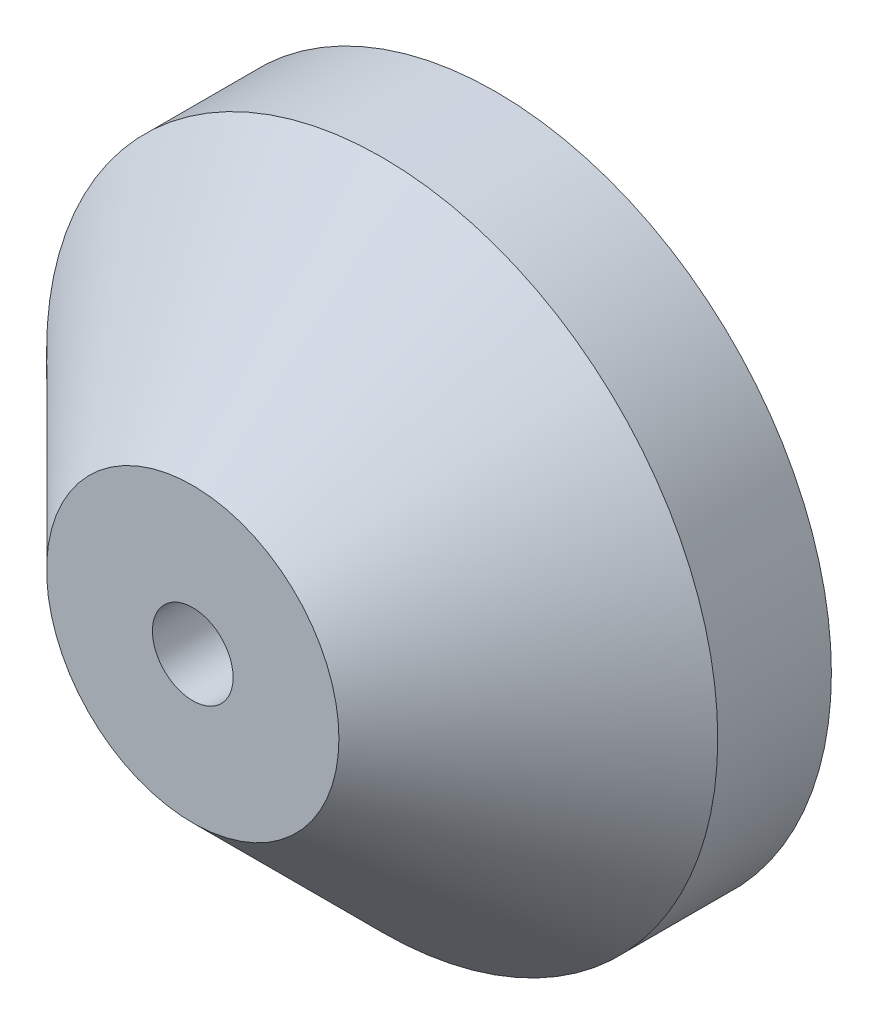
SolidWorks part; units mm, degrees
material "ABS"
ref_plane "Front Plane" through (0, 0, 0) normal (0, 0, 1) x (1, 0, 0)
ref_plane "Top Plane" through (0, 0, 0) normal (0, 1, 0) x (1, 0, 0)
ref_plane "Right Plane" through (0, 0, 0) normal (1, 0, 0) x (0, 0, -1)
sketch "Sketch1" plane through (0, 0, 0) normal (0, 0, 1) x (1, 0, 0)
  circle A0 centre (0, 0) radius 22.5
  dimension "D1" = 45
extrude "Boss-Extrude1" add sketch "Sketch1" against normal blind 20.32
sketch "Sketch2" plane through (0, 0, -20.32) normal (0, 0, -1) x (-1, 0, 0)
  circle A0 centre (0, 0) radius 17.5
  dimension "D1" = 35
extrude "Cut-Extrude1" cut sketch "Sketch2" against normal blind 11
sketch "Sketch5" plane through (0, 0, 0) normal (0, 0, 1) x (1, 0, 0)
  point P0 (0, 0)
hole_wizard "1/4-28 Tapped Hole1" positions "Sketch7" profile "Sketch8" tap size "1/4-28" standard "ANSI Inch" end condition up to next
sketch "Sketch7" plane through (0, 0, 0) normal (0, 0, 1) x (1, 0, 0)
  point P0 (0, 0)
sketch "Sketch8" plane through (0, 0, 0) normal (1, 0, 0) x (0, -1, 0)
  line L0 (0, 0) -> (0, 9.32)
  line L1 (0, 9.32) -> (2.7051, 9.32)
  line L2 (2.7051, 9.32) -> (2.7051, 0)
  line L5 (2.7051, 0) -> (0, 0)
  line L11 (0, -6.35) -> (0, 107.95) construction
  dimension "Thru Tap Drill Dia." = 5.4102
  dimension "Thru Tap Drill Depth" = 9.32
cosmetic thread "Hole Thread1" parameters "D2"=6.35
chamfer "Chamfer1" distance 12.7 angle 45 1 edges at (22.5, 0, 0)
